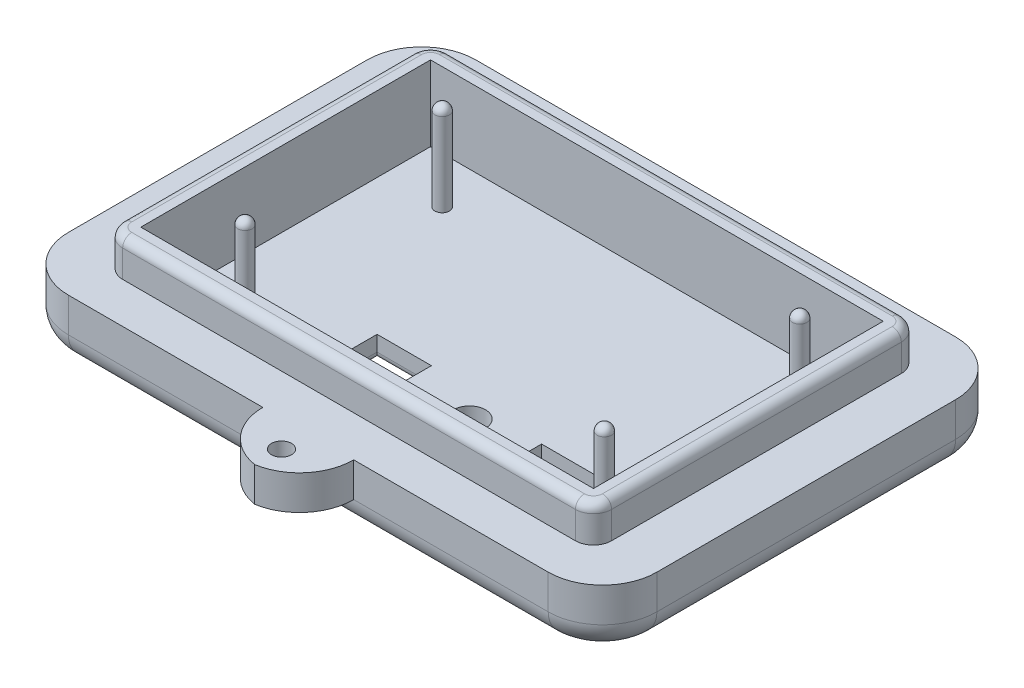
SolidWorks part; units mm, degrees
ref_plane "Front Plane" through (0, 0, 0) normal (0, 0, 1) x (1, 0, 0)
ref_plane "Top Plane" through (0, 0, 0) normal (0, 1, 0) x (1, 0, 0)
ref_plane "Right Plane" through (0, 0, 0) normal (1, 0, 0) x (0, 0, -1)
sketch "Sketch1" plane through (0, 0, 0) normal (0, 1, 0) x (1, 0, 0)
  line L1 (0, 0) -> (82.55, 0)
  line L2 (0, 0) -> (0, 57.15)
  line L3 (0, 57.15) -> (82.55, 57.15)
  line L4 (82.55, 0) -> (82.55, 57.15)
  dimension "D1" = 57.15
  dimension "D2" = 82.55
extrude "Boss-Extrude1" add sketch "Sketch1" along normal blind 8.636
fillet "Fillet2" radius 7.62 4 edges at (82.55, 4.318, -57.15) (82.55, 4.318, 0) (0, 4.318, 0) (0, 4.318, -57.15)
fillet "Fillet3" radius 3.81 8 edges at (80.3182, 0, -54.9182) (82.55, 0, -28.575) (80.3182, 0, -2.2318) (41.275, 0, 0) (2.2318, 0, -2.2318) (0, 0, -28.575) (2.2318, 0, -54.9182) (41.275, 0, -57.15)
sketch "Sketch2" plane through (0, 8.636, 0) normal (0, 1, 0) x (1, 0, 0)
  line L0 (0, 28.575) -> (82.55, 28.575) construction
  line L1 (0, 49.53) -> (0, 7.62) construction
  line L2 (82.55, 7.62) -> (82.55, 49.53) construction
  line L4 (9.525, 8.255) -> (73.025, 8.255)
  line L5 (9.525, 8.255) -> (9.525, 48.895)
  line L6 (9.525, 48.895) -> (73.025, 48.895)
  line L7 (73.025, 8.255) -> (73.025, 48.895)
  line L8 (9.525, 8.255) -> (73.025, 48.895) construction
  line L9 (9.525, 48.895) -> (73.025, 8.255) construction
  point P6 (41.275, 28.575)
  dimension "D1" = 40.64
  dimension "D2" = 63.5
extrude "Cut-Extrude1" cut sketch "Sketch2" against normal blind 5.461
sketch "Sketch7" plane through (0, 8.636, 0) normal (0, 1, 0) x (1, 0, 0)
  line L14 (6.985, 51.435) -> (6.985, 5.715)
  line L15 (6.985, 5.715) -> (75.565, 5.715)
  line L16 (75.565, 5.715) -> (75.565, 51.435)
  line L17 (75.565, 51.435) -> (6.985, 51.435)
  line L18 (6.985, 51.435) -> (6.985, 5.715)
  line L19 (6.985, 5.715) -> (75.565, 5.715)
  line L20 (75.565, 5.715) -> (75.565, 51.435)
  line L21 (75.565, 51.435) -> (6.985, 51.435)
  dimension "D1" = 2.54
extrude "Boss-Extrude3" add sketch "Sketch7" along normal blind 5.08
sketch "Sketch8" plane through (0, 13.716, 0) normal (0, 1, 0) x (1, 0, 0)
  line L8 (73.025, 48.895) -> (9.525, 48.895)
  line L9 (9.525, 48.895) -> (9.525, 8.255)
  line L10 (9.525, 8.255) -> (73.025, 8.255)
  line L11 (73.025, 8.255) -> (73.025, 48.895)
  line L12 (73.025, 48.895) -> (9.525, 48.895)
  line L13 (9.525, 48.895) -> (9.525, 8.255)
  line L14 (9.525, 8.255) -> (73.025, 8.255)
  line L15 (73.025, 8.255) -> (73.025, 48.895)
  dimension "D1" = 2.54
extrude "Cut-Extrude3" cut sketch "Sketch8" against normal blind 5.08
sketch "Sketch5" plane through (0, 3.175, 0) normal (0, 1, 0) x (1, 0, 0)
  line L3 (9.525, 8.255) -> (73.025, 8.255) construction
  line L4 (73.025, 8.255) -> (73.025, 48.895) construction
  circle A0 centre (17.665, 42.392) radius 1.016
  circle A1 centre (17.665, 14.732) radius 1.016
  circle A2 centre (67.945, 42.259) radius 1.016
  circle A3 centre (67.945, 14.859) radius 1.016
  dimension "D5" = 2.032
  dimension "D6" = 2.032
  dimension "D7" = 2.032
  dimension "D8" = 2.032
  dimension "D11" = 6.604
  dimension "D2" = 27.66
  dimension "D3" = 6.477
  dimension "D4" = 50.28
  dimension "D9" = 27.4
  dimension "D10" = 5.08
  dimension "D12" = 5.08
  dimension "D13" = 50.28
extrude "Boss-Extrude4" add sketch "Sketch5" along normal blind 12.7
sketch "Sketch4" plane through (0, 3.175, 0) normal (0, 1, 0) x (1, 0, 0)
  line L0 (75.565, 5.715) -> (75.565, 51.435) construction
  line L1 (75.565, 5.715) -> (75.565, 51.435) construction
  line L4 (66.04, 20.559) -> (53.44, 20.559)
  line L5 (66.04, 20.559) -> (66.04, 15.559)
  line L6 (66.04, 15.559) -> (53.44, 15.559)
  line L7 (53.44, 20.559) -> (53.44, 15.559)
  line L8 (66.04, 20.559) -> (53.44, 15.559) construction
  line L9 (66.04, 15.559) -> (53.44, 20.559) construction
  line L11 (36.195, 22.352) -> (28.575, 22.352)
  line L12 (36.195, 22.352) -> (36.195, 14.732)
  line L13 (36.195, 14.732) -> (28.575, 14.732)
  line L14 (28.575, 22.352) -> (28.575, 14.732)
  line L15 (36.195, 22.352) -> (28.575, 14.732) construction
  line L16 (36.195, 14.732) -> (28.575, 22.352) construction
  circle A0 centre (45.339, 18.542) radius 2.25
  circle A1 centre (17.665, 14.732) radius 1.016 construction
  circle A2 centre (67.945, 14.859) radius 1.016 construction
  point P7 (59.74, 18.059)
  point P15 (32.385, 18.542)
  dimension "D3" = 4.5
  dimension "D4" = 5.7
  dimension "D2" = 30.226
  dimension "D5" = 12.6
  dimension "D6" = 5
  dimension "D7" = 9.525
  dimension "D8" = 7.62
  dimension "D9" = 7.62
  dimension "D10" = 0
  dimension "D11" = 39.37
  dimension "D13" = 0
extrude "Cut-Extrude2" cut sketch "Sketch4" against normal blind 7.366
fillet "Fillet7" radius 1.016 3 edges at (17.665, 15.875, -13.716) (17.665, 15.875, -41.376) (67.945, 15.875, -41.243)
fillet "Fillet8" radius 2.54 4 edges at (75.565, 11.176, -51.435) (75.565, 11.176, -5.715) (6.985, 11.176, -5.715) (6.985, 11.176, -51.435)
sketch "Sketch9" plane through (0, 0, 0) normal (0, 0, 1) x (1, 0, 0)
  line L0 (41.275, 8.636) -> (41.275, 3.81) construction
  line L1 (7.62, 8.636) -> (74.93, 8.636) construction
  line L2 (7.62, 3.81) -> (74.93, 3.81) construction
  line L4 (47.6519, 8.636) -> (34.8981, 8.636)
  line L5 (47.6519, 8.636) -> (47.6519, 3.81)
  line L6 (47.6519, 3.81) -> (34.8981, 3.81)
  line L7 (34.8981, 8.636) -> (34.8981, 3.81)
  line L8 (47.6519, 8.636) -> (34.8981, 3.81) construction
  line L9 (47.6519, 3.81) -> (34.8981, 8.636) construction
  point P6 (41.275, 6.223)
  dimension "D1" = 12.7538
extrude "Boss-Extrude5" add sketch "Sketch9" along normal blind 7.62
fillet "Fillet10" radius 7.62 2 edges at (47.6519, 6.223, 7.62) (34.8981, 6.223, 7.62)
fillet "Fillet11" radius 1.27 8 edges at (74.8211, 13.716, -50.6911) (75.565, 13.716, -28.575) (74.8211, 13.716, -6.4589) (41.275, 13.716, -5.715) (7.7289, 13.716, -6.4589) (7.7289, 13.716, -50.6911) (6.985, 13.716, -28.575) (41.275, 13.716, -51.435)
fillet "Fillet12" radius 1.016 1 edges at (67.945, 15.875, -13.843)
sketch "Sketch17" plane through (0, 3.81, 0) normal (0, -1, 0) x (1, 0, 0)
  line L0 (41.275, 7.5179) -> (41.275, 0) construction
  point P3 (41.275, 3.759)
hole_wizard "#4-40 Tapped Hole2" positions "Sketch18" profile "Sketch19" tap size "#4-40" standard "ANSI Inch"
sketch "Sketch18" plane through (0, 3.81, 0) normal (0, -1, 0) x (-1, 0, 0)
  point P0 (-41.275, -3.759)
cosmetic thread "Hole Thread2" parameters "D1"=4.826, "D2"=2.8448
sketch "Sketch19" plane through (41.275, 3.81, 3.759) normal (1, 0, 0) x (0, 0, -1)
  line L0 (0, 0) -> (0, 8.4594)
  line L1 (0, 8.4594) -> (1.397, 7.62)
  line L2 (1.397, 7.62) -> (1.397, 0.5541)
  line L3 (1.397, 0.5541) -> (2.0574, 0)
  line L5 (2.0574, 0) -> (0, 0)
  line L6 (-1.397, 0.5541) -> (-2.0574, 0) construction
  line L10 (0, 8.4594) -> (-1.397, 7.62) construction
  line L11 (0, -6.35) -> (0, 107.95) construction
  dimension "Tap Drill Dia." = 2.794
  dimension "Tap Drill Depth" = 7.62
  dimension "Near C'Sink Dia." = 4.1148
  dimension "Near C'Sink Angle" = 100
  dimension "Drill Angle" = 118
fillet "Fillet13" radius 1.016 9 edges at (66.04, 0, -18.059) (59.74, 0, -15.559) (53.44, 0, -18.059) (59.74, 0, -20.559) (45.339, 0, -20.792) (28.575, 0, -18.542) (32.385, 0, -14.732) (36.195, 0, -18.542) (32.385, 0, -22.352)
